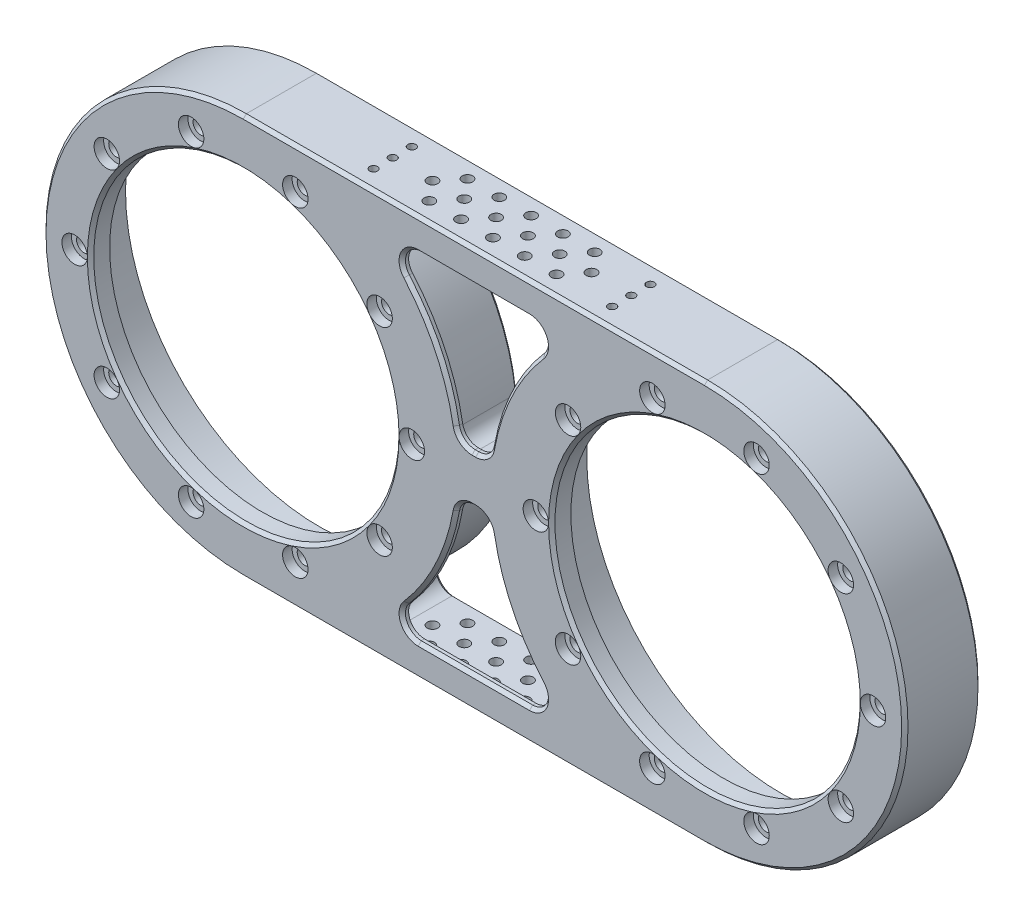
SolidWorks part; units mm, degrees
material "6061 合金"
ref_plane "前视基准面" through (0, 0, 0) normal (0, 0, 1) x (1, 0, 0)
ref_plane "上视基准面" through (0, 0, 0) normal (0, 1, 0) x (1, 0, 0)
ref_plane "右视基准面" through (0, 0, 0) normal (1, 0, 0) x (0, 0, -1)
sketch "草图1" plane through (0, 0, 0) normal (0, 0, 1) x (1, 0, 0)
  line L0 (0, 63) -> (145, 63)
  line L1 (0, -63) -> (145, -63)
  arc A0 (0, 63) -> (0, -63) centre (0, 0) ccw
  arc A1 (145, -63) -> (145, 63) centre (145, 0) ccw
  circle A2 centre (0, 0) radius 60
  circle A3 centre (145, 0) radius 60
extrude "凸台-拉伸1" add sketch "草图1" against normal blind 3
sketch "草图2" plane through (0, 0, 0) normal (0, 0, 1) x (1, 0, 0)
  line L2 (0, -63) -> (145, -63)
  line L3 (145, 63) -> (0, 63)
  line L4 (0, -63) -> (145, -63)
  line L5 (145, 63) -> (0, 63)
  circle A0 centre (0, 0) radius 53 construction
  circle A1 centre (145, 0) radius 53 construction
  circle A2 centre (0, 0) radius 48
  circle A3 centre (145, 0) radius 48
  arc A6 (0, 63) -> (0, -63) centre (0, 0) ccw
  arc A7 (145, -63) -> (145, 63) centre (145, 0) ccw
  arc A8 (0, 63) -> (0, -63) centre (0, 0) ccw
  arc A9 (145, -63) -> (145, 63) centre (145, 0) ccw
  dimension "D1" = 5
  dimension "D2" = 5
  dimension "D3" = 0
extrude "凸台-拉伸2" add sketch "草图2" along normal blind 6
sketch "草图3" plane through (0, 0, -3) normal (0, 0, -1) x (-1, 0, 0)
  line L2 (0, 63) -> (-145, 63)
  line L3 (-145, -63) -> (0, -63)
  line L4 (0, 63) -> (-145, 63)
  line L5 (-145, -63) -> (0, -63)
  circle A0 centre (-145, 0) radius 61
  circle A1 centre (0, 0) radius 61
  arc A4 (0, -63) -> (0, 63) centre (0, 0) ccw
  arc A5 (-145, 63) -> (-145, -63) centre (-145, 0) ccw
  arc A6 (0, -63) -> (0, 63) centre (0, 0) ccw
  arc A7 (-145, 63) -> (-145, -63) centre (-145, 0) ccw
  dimension "D1" = 0
extrude "凸台-拉伸3" add sketch "草图3" along normal blind 15
sketch "草图4" plane through (0, 0, -18) normal (0, 0, -1) x (-1, 0, 0)
  line L0 (-84, 0) -> (-61, 0) construction
  line L1 (0, 58) -> (-145, 58)
  line L2 (0, 63) -> (-145, 63)
  line L3 (-145, -63) -> (0, -63)
  line L4 (0, 63) -> (-145, 63)
  line L5 (-145, -63) -> (0, -63)
  line L6 (-145, -58) -> (0, -58)
  line L7 (-84, -2.5) -> (-61, -2.5)
  line L8 (-84, 2.5) -> (-61, 2.5)
  circle A0 centre (0, 0) radius 61 construction
  circle A1 centre (-145, 0) radius 61 construction
  circle A2 centre (0, 0) radius 61
  circle A3 centre (-145, 0) radius 61
  circle A5 centre (-145, 0) radius 63
  arc A6 (0, -63) -> (0, 63) centre (0, 0) ccw
  arc A7 (-145, 63) -> (-145, -63) centre (-145, 0) ccw
  arc A8 (0, -63) -> (0, 63) centre (0, 0) ccw
  arc A9 (-145, 63) -> (-145, -63) centre (-145, 0) ccw
  circle A10 centre (0, 0) radius 63
  dimension "D2" = 5
  dimension "D1" = 0
  dimension "D3" = 5
  dimension "D4" = 2.5
  dimension "D5" = 2.5
extrude "切除-拉伸1" cut sketch "草图4" against normal blind 22
sketch "草图7" plane through (0, 0, 4) normal (0, 0, -1) x (-1, 0, 0)
  line L6 (-42.6028, 53) -> (-102.3972, 53)
  line L7 (-77.4149, 7.5) -> (-67.5851, 7.5)
  line L8 (-42.6028, 53) -> (-102.3972, 53)
  line L9 (-77.4149, 7.5) -> (-67.5851, 7.5)
  line L12 (-67.5851, -7.5) -> (-77.4149, -7.5)
  line L13 (-102.3972, -53) -> (-42.6028, -53)
  line L14 (-67.5851, -7.5) -> (-77.4149, -7.5)
  line L15 (-102.3972, -53) -> (-42.6028, -53)
  arc A6 (-42.6028, 53) -> (-67.5851, 7.5) centre (0, 0) ccw
  arc A7 (-77.4149, 7.5) -> (-102.3972, 53) centre (-145, 0) ccw
  arc A8 (-42.6028, 53) -> (-67.5851, 7.5) centre (0, 0) ccw
  arc A9 (-77.4149, 7.5) -> (-102.3972, 53) centre (-145, 0) ccw
  arc A12 (-67.5851, -7.5) -> (-42.6028, -53) centre (0, 0) ccw
  arc A13 (-102.3972, -53) -> (-77.4149, -7.5) centre (-145, 0) ccw
  arc A14 (-67.5851, -7.5) -> (-42.6028, -53) centre (0, 0) ccw
  arc A15 (-102.3972, -53) -> (-77.4149, -7.5) centre (-145, 0) ccw
  dimension "D1" = 5
  dimension "D2" = 5
extrude "切除-拉伸2" cut sketch "草图7" against normal blind 20
fillet "圆角2" radius 5 16 edges at (67.5851, 7.5, 5) (77.4149, 7.5, 5) (42.6028, -53, 5) (102.3972, -53, 5) (77.4149, -7.5, 5) (67.5851, -7.5, 5) (42.6028, 53, 5) (102.3972, 53, 5) (82.0496, 2.5, -7) (62.9504, 2.5, -7) (24.5967, 58, -7) (82.0496, -2.5, -7) (120.4033, -58, -7) (24.5967, -58, -7) (62.9504, -2.5, -7) (120.4033, 58, -7)
chamfer "倒角2" distance 1 angle 45 44 edges at (193, 0, 6) (72.5, 63, 6) (208, 0, 6) (72.5, -63, 6) (-63, 0, 6) (48, 0, 6) (68.7032, 8.6737, 6) (72.5, 7.5, 6) (76.2968, 8.6737, 6) (83.6169, 29.2595, 6) (94.5518, 50.069, 6) (72.5, 53, 6) (50.4482, 50.069, 6) (61.3831, 29.2595, 6) (50.4482, -50.069, 6) (72.5, -53, 6) (94.5518, -50.069, 6) (83.6169, -29.2595, 6) (76.2968, -8.6737, 6) (72.5, -7.5, 6) (68.7032, -8.6737, 6) (61.3831, -29.2595, 6) (60, 0, -3) (205, 0, -3) (89.7765, -30.3211, -18) (80.7497, -3.7746, -18) (107.1134, -54.6605, -18) (72.5, -2.5, -18) (72.5, -58, -18) (64.2503, -3.7746, -18) (37.8866, -54.6605, -18) (55.2235, -30.3211, -18) (72.5, -63, -18) (-63, 0, -18) (208, 0, -18) (72.5, 63, -18) (72.5, 2.5, -18) (64.2503, 3.7746, -18) (80.7497, 3.7746, -18) (55.2235, 30.3211, -18) (89.7765, 30.3211, -18) (37.8866, 54.6605, -18) (107.1134, 54.6605, -18) (72.5, 58, -18)
sketch "草图8" plane through (0, 0, 6) normal (0, 0, 1) x (1, 0, 0)
  circle A0 centre (145, 0) radius 53 construction
  circle A1 centre (0, 0) radius 53 construction
  point P6 (198, 0)
  point P7 (53, 0)
hole_wizard "打孔尺寸(%根据)内六角圆柱头螺钉的类型1" positions "草图9" profile "草图10" counterbore size "M4" standard "GB"
sketch "草图9" plane through (0, 0, 6) normal (0, 0, 1) x (1, 0, 0)
  point P0 (198, 0)
sketch "草图10" plane through (198, 0, 6) normal (1, 0, 0) x (0, -1, 0)
  line L0 (0, 0) -> (0, 11.5421)
  line L1 (0, 11.5421) -> (2.4, 10.1)
  line L2 (2.4, 10.1) -> (2.4, 3)
  line L3 (2.4, 3) -> (4, 3)
  line L4 (4, 3) -> (4, 0)
  line L5 (4, 0) -> (0, 0)
  line L10 (0, 11.5421) -> (-2.4, 10.1) construction
  line L11 (0, -6.35) -> (0, 107.95) construction
  dimension "孔直径" = 4.8
  dimension "孔深度" = 10.1
  dimension "柱形沉头孔直径" = 8
  dimension "柱形沉头孔深度" = 3
  dimension "导头角度" = 118
hole_wizard "打孔尺寸(%根据)内六角圆柱头螺钉的类型2" positions "草图11" profile "草图12" counterbore size "M4" standard "GB"
sketch "草图11" plane through (0, 0, 6) normal (0, 0, 1) x (1, 0, 0)
  point P0 (53, 0)
sketch "草图12" plane through (53, 0, 6) normal (1, 0, 0) x (0, -1, 0)
  line L0 (0, 0) -> (0, 11.5421)
  line L1 (0, 11.5421) -> (2.4, 10.1)
  line L2 (2.4, 10.1) -> (2.4, 3)
  line L3 (2.4, 3) -> (4, 3)
  line L4 (4, 3) -> (4, 0)
  line L5 (4, 0) -> (0, 0)
  line L10 (0, 11.5421) -> (-2.4, 10.1) construction
  line L11 (0, -6.35) -> (0, 107.95) construction
  dimension "孔直径" = 4.8
  dimension "孔深度" = 10.1
  dimension "柱形沉头孔直径" = 8
  dimension "柱形沉头孔深度" = 3
  dimension "导头角度" = 118
pattern_circular "阵列(圆周)1" count 10 every 36 about axis through (145, 0, 0) along (0, 0, 1) of "打孔尺寸(%根据)内六角圆柱头螺钉的类型1"
pattern_circular "阵列(圆周)2" count 10 every 36 about axis through (0, 0, 0) along (0, 0, 1) of "打孔尺寸(%根据)内六角圆柱头螺钉的类型2"
sketch "草图13" plane through (0, 63, 0) normal (0, 1, 0) x (1, 0, 0)
  line L0 (72.5, 18) -> (72.5, 12) construction
  line L1 (0, 18) -> (145, 18) construction
  line L2 (72.5, 12) -> (72.5, 6) construction
  line L4 (72.5, 6) -> (72.5, 0) construction
  line L5 (62.5, 12) -> (82.5, 12) construction
  line L6 (67.5, 6) -> (77.5, 6) construction
  line L7 (62.5, 0) -> (82.5, 0) construction
  line L8 (57.5, 6) -> (87.5, 6) construction
  line L9 (52.5, 12) -> (92.5, 12) construction
  line L10 (52.5, 0) -> (92.5, 0) construction
  line L11 (47.5, 6) -> (97.5, 6) construction
  point P7 (72.5, 12)
  point P12 (72.5, 6)
  point P17 (72.5, 0)
  point P20 (72.5, 6)
  point P23 (72.5, 12)
  point P25 (72.5, 0)
  point P30 (72.5, 6)
hole_wizard "M4 螺纹孔1" positions "草图17" profile "草图18" tap size "M4" standard "GB"
sketch "草图17" plane through (0, 63, 0) normal (0, 1, 0) x (1, 0, 0)
  point P5 (72.5, 12)
  point P8 (72.5, 0)
  point P11 (77.5, 6)
  point P14 (67.5, 6)
  point P17 (62.5, 12)
  point P20 (57.5, 6)
  point P23 (62.5, 0)
  point P26 (52.5, 0)
  point P29 (47.5, 6)
  point P32 (52.5, 12)
  point P35 (82.5, 12)
  point P38 (87.5, 6)
  point P41 (82.5, 0)
  point P44 (92.5, 0)
  point P47 (97.5, 6)
  point P50 (92.5, 12)
sketch "草图18" plane through (72.5, 63, -12) normal (1, 0, 0) x (0, 0, 1)
  line L0 (0, 0) -> (0, 11.0914)
  line L1 (0, 11.0914) -> (1.65, 10.1)
  line L2 (1.65, 10.1) -> (1.65, 0)
  line L5 (1.65, 0) -> (0, 0)
  line L10 (0, 11.0914) -> (-1.65, 10.1) construction
  line L11 (0, -6.35) -> (0, 107.95) construction
  dimension "螺纹孔钻头直径" = 3.3
  dimension "螺纹孔钻头深度" = 10.1
  dimension "导头角度" = 118
cosmetic thread "孔螺蚊线1" parameters "D1"=8, "D2"=4
cosmetic thread "孔螺蚊线2" parameters "D1"=8, "D2"=4
cosmetic thread "孔螺蚊线3" parameters "D1"=8, "D2"=4
cosmetic thread "孔螺蚊线4" parameters "D1"=8, "D2"=4
cosmetic thread "孔螺蚊线5" parameters "D1"=8, "D2"=4
cosmetic thread "孔螺蚊线6" parameters "D1"=8, "D2"=4
cosmetic thread "孔螺蚊线7" parameters "D1"=8, "D2"=4
cosmetic thread "孔螺蚊线8" parameters "D1"=8, "D2"=4
cosmetic thread "孔螺蚊线9" parameters "D1"=8, "D2"=4
cosmetic thread "孔螺蚊线10" parameters "D1"=8, "D2"=4
cosmetic thread "孔螺蚊线11" parameters "D1"=8, "D2"=4
cosmetic thread "孔螺蚊线12" parameters "D1"=8, "D2"=4
cosmetic thread "孔螺蚊线13" parameters "D1"=8, "D2"=4
cosmetic thread "孔螺蚊线14" parameters "D1"=8, "D2"=4
cosmetic thread "孔螺蚊线15" parameters "D1"=8, "D2"=4
cosmetic thread "孔螺蚊线16" parameters "D1"=8, "D2"=4
ref_plane "基准面1" through (0, 0, 0) normal (0, 1, 0) x (1, 0, 0)
mirror "镜向1" about plane through (0, 0, 0) normal (0, 1, 0) of "M4 螺纹孔1"
cosmetic thread "孔螺蚊线17" parameters "D1"=8, "D2"=4
cosmetic thread "孔螺蚊线18" parameters "D1"=8, "D2"=4
cosmetic thread "孔螺蚊线19" parameters "D1"=8, "D2"=4
cosmetic thread "孔螺蚊线20" parameters "D1"=8, "D2"=4
cosmetic thread "孔螺蚊线21" parameters "D1"=8, "D2"=4
cosmetic thread "孔螺蚊线22" parameters "D1"=8, "D2"=4
cosmetic thread "孔螺蚊线23" parameters "D1"=8, "D2"=4
cosmetic thread "孔螺蚊线24" parameters "D1"=8, "D2"=4
cosmetic thread "孔螺蚊线25" parameters "D1"=8, "D2"=4
cosmetic thread "孔螺蚊线26" parameters "D1"=8, "D2"=4
cosmetic thread "孔螺蚊线27" parameters "D1"=8, "D2"=4
cosmetic thread "孔螺蚊线28" parameters "D1"=8, "D2"=4
cosmetic thread "孔螺蚊线29" parameters "D1"=8, "D2"=4
cosmetic thread "孔螺蚊线30" parameters "D1"=8, "D2"=4
cosmetic thread "孔螺蚊线31" parameters "D1"=8, "D2"=4
cosmetic thread "孔螺蚊线32" parameters "D1"=8, "D2"=4
sketch "草图19" plane through (0, -63, 0) normal (0, -1, 0) x (1, 0, 0)
  line L0 (35, 0) -> (110, 0)
  line L2 (35, -12) -> (110, -12)
  line L4 (35, -6) -> (110, -6)
  line L6 (47.5, -6) -> (97.5, -6) construction
  point P4 (72.5, 0)
  point P11 (72.5, -12)
  point P15 (72.5, -6)
hole_wizard "M3 螺纹孔1" positions "草图20" profile "草图21" tap size "M3" standard "GB"
sketch "草图20" plane through (0, -63, 0) normal (0, -1, 0) x (-1, 0, 0)
  point P0 (-35, 0)
  point P3 (-35, 6)
  point P6 (-35, 12)
  point P9 (-110, 12)
  point P12 (-110, 6)
  point P15 (-110, 0)
sketch "草图21" plane through (35, -63, 0) normal (1, 0, 0) x (0, 0, -1)
  line L0 (0, 0) -> (0, 8.2511)
  line L1 (0, 8.2511) -> (1.25, 7.5)
  line L2 (1.25, 7.5) -> (1.25, 0)
  line L5 (1.25, 0) -> (0, 0)
  line L10 (0, 8.2511) -> (-1.25, 7.5) construction
  line L11 (0, -6.35) -> (0, 107.95) construction
  dimension "螺纹孔钻头直径" = 2.5
  dimension "螺纹孔钻头深度" = 7.5
  dimension "导头角度" = 118
cosmetic thread "孔螺蚊线33" parameters "D1"=6, "D2"=3
cosmetic thread "孔螺蚊线34" parameters "D1"=6, "D2"=3
cosmetic thread "孔螺蚊线35" parameters "D1"=6, "D2"=3
cosmetic thread "孔螺蚊线36" parameters "D1"=6, "D2"=3
cosmetic thread "孔螺蚊线37" parameters "D1"=6, "D2"=3
cosmetic thread "孔螺蚊线38" parameters "D1"=6, "D2"=3
mirror "镜向2" about plane through (0, 0, 0) normal (0, 1, 0) of "M3 螺纹孔1"
cosmetic thread "孔螺蚊线39" parameters "D1"=6, "D2"=3
cosmetic thread "孔螺蚊线40" parameters "D1"=6, "D2"=3
cosmetic thread "孔螺蚊线41" parameters "D1"=6, "D2"=3
cosmetic thread "孔螺蚊线42" parameters "D1"=6, "D2"=3
cosmetic thread "孔螺蚊线43" parameters "D1"=6, "D2"=3
cosmetic thread "孔螺蚊线44" parameters "D1"=6, "D2"=3
sketch "草图22" plane through (0, -63, 0) normal (0, -1, 0) x (1, 0, 0)
  line L0 (35, 0) -> (110, 0) construction
  point P5 (72.5, 0)
